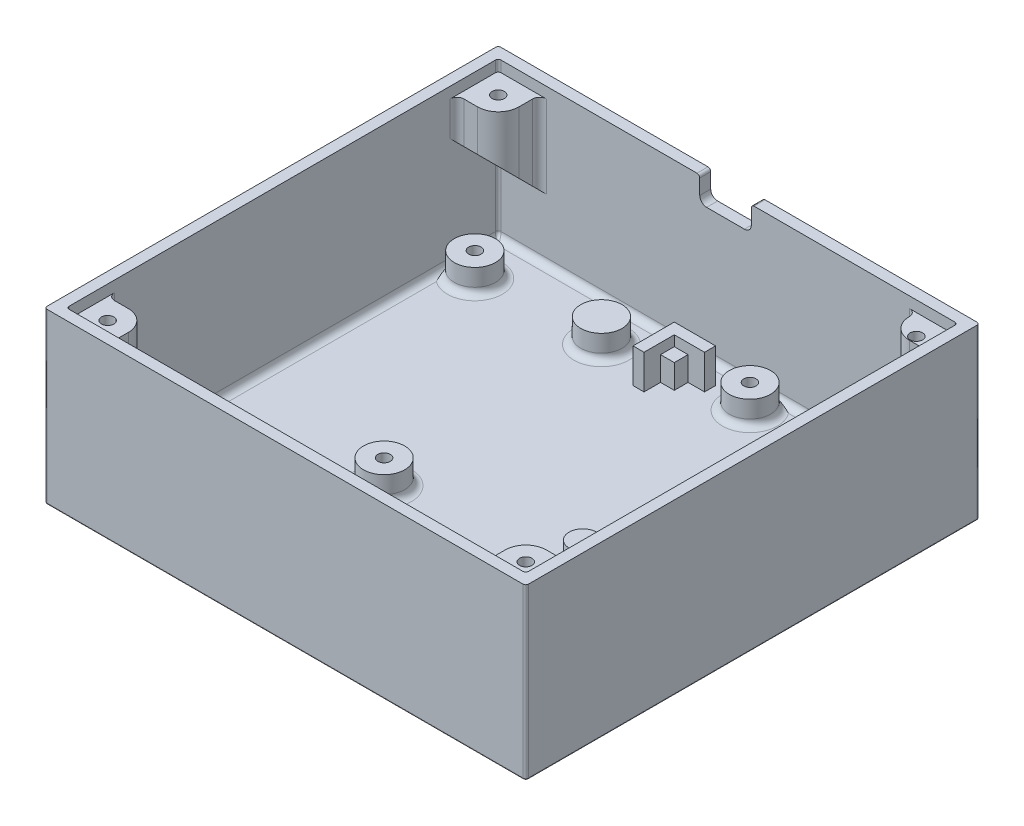
SolidWorks part; units mm, degrees
ref_plane "前视基准面" through (0, 0, 0) normal (0, 0, 1) x (1, 0, 0)
ref_plane "上视基准面" through (0, 0, 0) normal (0, 1, 0) x (1, 0, 0)
ref_plane "右视基准面" through (0, 0, 0) normal (1, 0, 0) x (0, 0, -1)
other "Configuration Table"
sketch "草图1" plane through (0, 0, 0) normal (0, 1, 0) x (1, 0, 0)
  line L1 (0, 0) -> (70, 0)
  line L2 (0, 0) -> (0, 66)
  line L3 (0, 66) -> (70, 66)
  line L4 (70, 0) -> (70, 66)
  dimension "D1" = 70
  dimension "D2" = 66
extrude "凸台-拉伸1" add sketch "草图1" along normal blind 2
sketch "草图2" plane through (0, 2, 0) normal (0, 1, 0) x (1, 0, 0)
  line L0 (70, 0) -> (70, 66) construction
  line L1 (66.8, 60) -> (31.6, 60)
  line L2 (66.8, 60) -> (66.8, 6)
  line L3 (66.8, 6) -> (31.6, 6)
  line L4 (31.6, 60) -> (31.6, 6)
  line L5 (70, 66) -> (0, 66) construction
  line L11 (68.4, 61.6) -> (30, 61.6)
  line L12 (30, 61.6) -> (30, 4.4)
  line L13 (68.4, 4.4) -> (30, 4.4)
  line L14 (68.4, 61.6) -> (68.4, 4.4)
  dimension "D1" = 35.2
  dimension "D2" = 54
  dimension "D3" = 3.2
  dimension "D4" = 6
  dimension "D5" = 1.6
extrude "凸台-拉伸2" add sketch "草图2" along normal blind 5
sketch "草图3" plane through (0, 2, 0) normal (0, 1, 0) x (1, 0, 0)
  line L0 (31.6, 6) -> (66.8, 6) construction
  line L1 (31.6, 60) -> (33.6, 60)
  line L2 (31.6, 60) -> (31.6, 58)
  line L3 (31.6, 58) -> (33.6, 58)
  line L4 (33.6, 60) -> (33.6, 58)
  line L5 (66.8, 60) -> (64.8, 60)
  line L6 (66.8, 60) -> (66.8, 58)
  line L7 (66.8, 58) -> (64.8, 58)
  line L8 (64.8, 60) -> (64.8, 58)
  line L9 (31.6, 6) -> (33.6, 6)
  line L10 (31.6, 6) -> (31.6, 8)
  line L11 (31.6, 8) -> (33.6, 8)
  line L12 (33.6, 6) -> (33.6, 8)
  line L13 (66.8, 6) -> (64.8, 6)
  line L14 (66.8, 6) -> (66.8, 8)
  line L15 (66.8, 8) -> (64.8, 8)
  line L16 (64.8, 6) -> (64.8, 8)
  line L17 (66.8, 6) -> (66.8, 60) construction
  circle A0 centre (49.3, 29) radius 2
  dimension "D9" = 4
  dimension "D11" = 17.5
  dimension "D1" = 2
  dimension "D2" = 2
  dimension "D3" = 2
  dimension "D4" = 2
  dimension "D5" = 2
  dimension "D6" = 2
  dimension "D7" = 2
  dimension "D8" = 2
  dimension "D10" = 23
extrude "凸台-拉伸3" add sketch "草图3" along normal blind 3.5
sketch "草图4" plane through (0, 7, 0) normal (0, 1, 0) x (1, 0, 0)
  line L0 (68.4, 61.6) -> (30, 61.6) construction
  line L1 (36, 61.6) -> (62.4, 61.6)
  line L2 (36, 61.6) -> (36, 60)
  line L3 (36, 60) -> (62.4, 60)
  line L4 (62.4, 61.6) -> (62.4, 60)
  line L5 (64.8, 60) -> (33.6, 60) construction
  line L6 (30, 61.6) -> (30, 4.4) construction
  line L7 (30, 55.6) -> (31.6, 55.6)
  line L8 (30, 55.6) -> (30, 10.4)
  line L9 (30, 10.4) -> (31.6, 10.4)
  line L10 (31.6, 55.6) -> (31.6, 10.4)
  line L11 (31.6, 58) -> (31.6, 8) construction
  line L12 (31.6, 6) -> (66.8, 6) construction
  line L13 (36, 6) -> (62.4, 6)
  line L14 (36, 6) -> (36, 4.4)
  line L15 (36, 4.4) -> (62.4, 4.4)
  line L16 (62.4, 6) -> (62.4, 4.4)
  line L17 (30, 4.4) -> (68.4, 4.4) construction
  line L18 (30, 61.6) -> (30, 4.4) construction
  line L19 (68.4, 4.4) -> (68.4, 61.6) construction
  line L20 (66.8, 6) -> (66.8, 60) construction
  line L21 (66.8, 55.6) -> (68.4, 55.6)
  line L22 (66.8, 55.6) -> (66.8, 10.4)
  line L23 (66.8, 10.4) -> (68.4, 10.4)
  line L24 (68.4, 55.6) -> (68.4, 10.4)
  line L25 (68.4, 61.6) -> (30, 61.6) construction
  dimension "D1" = 6
  dimension "D2" = 6
  dimension "D3" = 6
  dimension "D4" = 6
  dimension "D5" = 6
  dimension "D6" = 6
  dimension "D7" = 6
  dimension "D8" = 6
extrude "切除-拉伸1" cut sketch "草图4" against normal up to surface (5 mm away) up to face at (35, 2, -33)
sketch "草图8" plane through (0, 2, 0) normal (0, 1, 0) x (1, 0, 0)
  line L0 (70, 66) -> (0, 66) construction
  line L1 (30, 10.4) -> (30, 4.4) construction
  line L2 (30, 61.6) -> (30, 55.6) construction
  line L3 (30, 4.4) -> (36, 4.4) construction
  line L4 (36, 61.6) -> (30, 61.6) construction
  line L5 (68.4, 4.4) -> (68.4, 10.4) construction
  line L6 (62.4, 6) -> (66.8, 6) construction
  line L8 (31.6, 60) -> (31.6, 55.6) construction
  line L9 (36, 60) -> (31.6, 60) construction
  circle A1 centre (5, 57.6) radius 3
  circle A3 centre (24.5, 24.9) radius 3
  circle A5 centre (6.3, 14.4) radius 3
  circle A7 centre (22.5, 58.5) radius 3
  circle A8 centre (49.4, 5) radius 3
  circle A9 centre (41.6, 61) radius 3
  dimension "D4" = 6
  dimension "D7" = 6
  dimension "D8" = 5.5
  dimension "D9" = 20.5
  dimension "D10" = 6
  dimension "D11" = 23.7
  dimension "D12" = 10
  dimension "D14" = 6
  dimension "D16" = 7.5
  dimension "D5" = 25
  dimension "D6" = 4
  dimension "D17" = 6
  dimension "D18" = 19
  dimension "D19" = 1
  dimension "D20" = 6
  dimension "D21" = 10
  dimension "D22" = 1
  dimension "D23" = 7.5
extrude "凸台-拉伸9" add sketch "草图8" along normal blind 3.5
sketch "草图9" plane through (0, 2, 0) normal (0, 1, 0) x (1, 0, 0)
  line L0 (1.6, 64.4) -> (1.6, 1.6)
  line L1 (0, 66) -> (70, 66)
  line L2 (0, 66) -> (0, 0)
  line L3 (0, 0) -> (70, 0)
  line L4 (70, 66) -> (70, 0)
  line L5 (1.6, 1.6) -> (68.4, 1.6)
  line L6 (68.4, 64.4) -> (68.4, 1.6)
  line L7 (1.6, 64.4) -> (68.4, 64.4)
  line L8 (70, 0) -> (70, 66) construction
  line L9 (0, 0) -> (70, 0) construction
  dimension "D2" = 0
  dimension "D3" = 0
  dimension "D1" = 1.6
extrude "凸台-拉伸13" add sketch "草图9" along normal blind 21
sketch "草图11" plane through (0, 23, 0) normal (0, 1, 0) x (1, 0, 0)
  line L0 (68.4, 64.4) -> (1.6, 64.4) construction
  line L1 (68.4, 64.4) -> (62.4, 64.4)
  line L2 (68.4, 64.4) -> (68.4, 60.4)
  line L3 (68.4, 60.4) -> (62.4, 60.4)
  line L4 (62.4, 64.4) -> (62.4, 60.4)
  line L5 (68.4, 61.6) -> (68.4, 64.4) construction
  line L7 (68.4, 1.6) -> (62.4, 1.6)
  line L8 (68.4, 1.6) -> (68.4, 7.6)
  line L9 (68.4, 7.6) -> (62.4, 7.6)
  line L10 (62.4, 1.6) -> (62.4, 7.6)
  line L11 (1.6, 1.6) -> (7.6, 1.6)
  line L12 (1.6, 1.6) -> (1.6, 7.6)
  line L13 (1.6, 7.6) -> (7.6, 7.6)
  line L14 (7.6, 1.6) -> (7.6, 7.6)
  line L15 (1.6, 64.4) -> (7.6, 64.4)
  line L16 (1.6, 64.4) -> (1.6, 58.4)
  line L17 (1.6, 58.4) -> (7.6, 58.4)
  line L18 (7.6, 64.4) -> (7.6, 58.4)
  dimension "D1" = 4
  dimension "D2" = 6
  dimension "D3" = 6
  dimension "D4" = 6
  dimension "D5" = 6
  dimension "D6" = 6
  dimension "D7" = 6
  dimension "D8" = 6
extrude "凸台-拉伸14" add sketch "草图11" against normal blind 6
chamfer "倒角1" distance 6 angle 45 4 edges at (65.4, 17, -64.4) (4.6, 17, -64.4) (65.4, 17, -1.6) (4.6, 17, -1.6)
sketch "草图12" plane through (0, 23, 0) normal (0, 1, 0) x (1, 0, 0)
  line L0 (1.6, 64.4) -> (1.6, 1.6)
  line L1 (0, 66) -> (70, 66)
  line L2 (0, 66) -> (0, 0)
  line L3 (0, 0) -> (70, 0)
  line L4 (70, 66) -> (70, 0)
  line L5 (1.6, 1.6) -> (68.4, 1.6)
  line L6 (68.4, 64.4) -> (68.4, 1.6)
  line L7 (1.6, 64.4) -> (68.4, 64.4)
  dimension "D1" = 1.6
extrude "凸台-拉伸15" add sketch "草图12" along normal blind 1.6
sketch "草图13" plane through (0, 23, 0) normal (0, 1, 0) x (1, 0, 0)
  line L0 (1.6, 58.4) -> (7.6, 58.4) construction
  line L1 (7.6, 58.4) -> (7.6, 64.4) construction
  circle A0 centre (4.6, 61.4) radius 0.9
  circle A1 centre (65.4, 61.4) radius 0.9
  circle A2 centre (65.4, 4.6) radius 0.9
  circle A3 centre (4.6, 4.6) radius 0.9
  dimension "D1" = 1.8
  dimension "D2" = 3
  dimension "D3" = 3
  dimension "D4" = 2
  dimension "D5" = 2
extrude "切除-拉伸3" cut sketch "草图13" against normal blind 6
sketch "草图14" plane through (0, 0, -64.4) normal (0, 0, 1) x (1, 0, 0)
  line L1 (30.9, 24.6) -> (38.4, 24.6)
  line L2 (30.9, 24.6) -> (30.9, 21)
  line L3 (30.9, 21) -> (38.4, 21)
  line L4 (38.4, 24.6) -> (38.4, 21)
  line L5 (68.4, 24.6) -> (1.6, 24.6) construction
  dimension "D1" = 3.6
  dimension "D2" = 7.5
  dimension "D3" = 0
  dimension "D4" = 30
extrude "切除-拉伸4" cut sketch "草图14" against normal blind 6
fillet "圆角1" radius 1 35 edges at (33.6, 2, -7) (32.6, 2, -8) (31.6, 2, -9.2) (30.8, 2, -10.4) (30, 2, -7.4) (33, 2, -4.4) (36, 2, -5.2) (34.8, 2, -6) (5, 2, -60.6) (24.5, 2, -27.9) (6.3, 2, -17.4) (49.4, 2, -8) (41.6, 2, -64) (49.3, 2, -31) (22.5, 2, -61.5) (65.4, 2, -4.4) (62.4, 2, -5.2) (63.6, 2, -6) (64.8, 2, -7) (65.8, 2, -8) (66.8, 2, -9.2) (67.6, 2, -10.4) (65.4, 2, -61.6) (67.6, 2, -55.6) (66.8, 2, -56.8) (65.8, 2, -58) (64.8, 2, -59) (63.6, 2, -60) (62.4, 2, -60.8) (35, 2, -64.4) (68.4, 2, -63) (68.4, 2, -33) (68.4, 2, -3) (35, 2, -1.6) (1.6, 2, -33)
fillet "圆角2" radius 1 2 edges at (38.4, 21, -65.2) (30.9, 21, -65.2)
fillet "圆角3" radius 3 4 edges at (7.6, 20, -7.6) (62.4, 20, -7.6) (62.4, 19, -60.4) (7.6, 20, -58.4)
fillet "圆角4" radius 1 8 edges at (1.6, 20, -7.6) (7.6, 17, -1.6) (62.4, 17, -1.6) (68.4, 20, -7.6) (68.4, 19, -60.4) (62.4, 17, -64.4) (1.6, 20, -58.4) (7.6, 17, -64.4)
fillet "圆角5" radius 0.4 18 edges at (68.1071, 2.2929, -64.1071) (1.8929, 2.2929, -64.1071) (1.8929, 2.2929, -1.8929) (68.1071, 2.2929, -1.8929) (68.4, 23.8, -1.6) (68.4, 7, -64.4) (68.4, 23.8, -64.4) (1.6, 23.8, -64.4) (1.6, 7, -64.4) (1.6, 23.8, -1.6) (1.6, 7, -1.6) (68.4, 7, -1.6) (0, 12.3, 0) (70, 12.3, 0) (70, 12.3, -66) (0, 12.3, -66) (30.9, 24.6, -65.2) (38.4, 24.6, -65.2)
fillet "圆角6" radius 0.2 8 edges at (69.8828, 0, -0.1172) (70, 0, -33) (69.8828, 0, -65.8828) (35, 0, -66) (0.1172, 0, -65.8828) (0, 0, -33) (0.1172, 0, -0.1172) (35, 0, 0)
sketch "草图18" plane through (0, 5.5, 0) normal (0, 1, 0) x (1, 0, 0)
  circle A0 centre (41.6, 61) radius 0.9
  circle A1 centre (49.4, 5) radius 0.9
  dimension "D1" = 1.8
  dimension "D2" = 1.8
extrude "切除-拉伸7" cut sketch "草图18" against normal blind 6
sketch "草图19" plane through (0, 5.5, 0) normal (0, 1, 0) x (1, 0, 0)
  circle A0 centre (5, 57.6) radius 0.9
  circle A1 centre (24.5, 24.9) radius 0.9
  dimension "D1" = 1.8
  dimension "D2" = 1.8
extrude "切除-拉伸8" cut sketch "草图19" against normal blind 6
